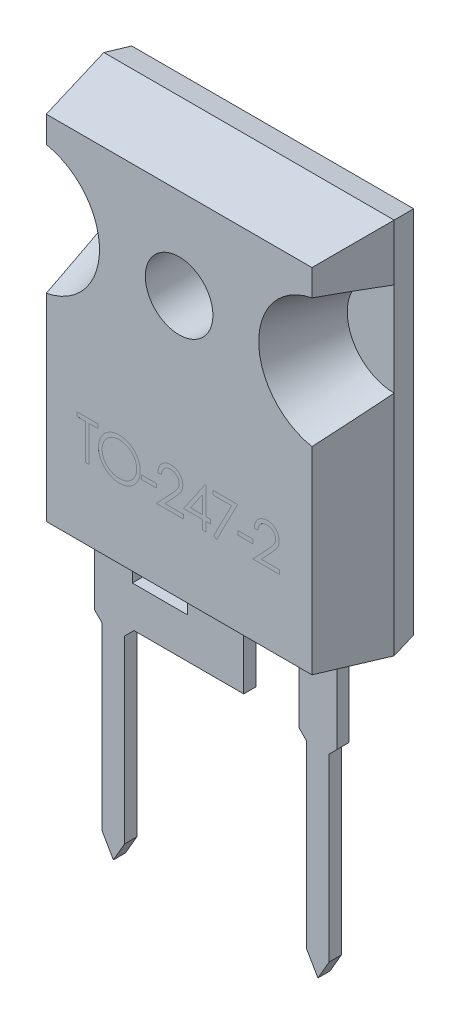
SolidWorks part; units mm, degrees
ref_plane "Front Plane" through (0, 0, 0) normal (0, 0, 1) x (1, 0, 0)
ref_plane "Top Plane" through (0, 0, 0) normal (0, 1, 0) x (1, 0, 0)
ref_plane "Right Plane" through (0, 0, 0) normal (1, 0, 0) x (0, 0, -1)
sketch "Sketch1" plane through (0, 0, 0) normal (0, 0, 1) x (1, 0, 0)
  line L1 (-7.75, 10.075) -> (7.75, 10.075)
  line L2 (-7.75, 10.075) -> (-7.75, -10.075)
  line L3 (-7.75, -10.075) -> (7.75, -10.075)
  line L4 (7.75, 10.075) -> (7.75, -10.075)
  line L5 (-7.75, 10.075) -> (7.75, -10.075) construction
  line L6 (-7.75, -10.075) -> (7.75, 10.075) construction
  point P0 (0, 0)
  dimension "D1" = 15.5
  dimension "D2" = 20.15
extrude "Boss-Extrude1" add sketch "Sketch1" against normal blind 1.27 draft 10 and the other way blind 3.73 draft 10
sketch "Sketch2" plane through (0, 0, 0) normal (0, 0, 1) x (1, 0, 0)
  line L0 (7.75, 10.075) -> (-7.75, 10.075) construction
  line L1 (-5.25, 7.4139) -> (-5.25, 0.8413) construction
  line L2 (-7.75, 10.075) -> (-7.75, -10.075) construction
  line L3 (0, 14.1994) -> (0, -3.2617) construction
  line L4 (7.75, -10.075) -> (7.75, 10.075) construction
  circle A0 centre (0, 4.565) radius 1.805 construction
  circle A1 centre (-7.75, 4.575) radius 2.5
  circle A2 centre (7.75, 4.575) radius 2.5
  dimension "D1" = 5.51
  dimension "D2" = 3.61
  dimension "D3" = 5.5
  dimension "D4" = 5
  dimension "D5" = 2.5
  dimension "D6" = 7.75
extrude "Cut-Extrude1" cut sketch "Sketch2" along normal up to surface (3.73 mm away) draft 15
sketch "Sketch4" plane through (0, 0, 0) normal (0, 0, 1) x (1, 0, 0)
  line L0 (7.75, 10.075) -> (-7.75, 10.075) construction
  circle A0 centre (0, 4.565) radius 1.805
  dimension "D1" = 3.61
  dimension "D2" = 5.51
extrude "Cut-Extrude2" cut sketch "Sketch4" along normal through all both and the other way through all
sketch "Sketch5" plane through (0, 0, 0) normal (0, 1, 0) x (1, 0, 0)
  line L0 (-9.5483, -1.13) -> (8.845, -1.13) construction
  line L1 (7.5261, 1.27) -> (-7.5261, 1.27) construction
  line L2 (0, 2.9425) -> (0, -4.6836) construction
  line L3 (-6.47, -1.13) -> (-4.45, -1.13)
  line L4 (-6.47, -1.13) -> (-6.47, -1.78)
  line L5 (-6.47, -1.78) -> (-4.45, -1.78)
  line L6 (-4.45, -1.13) -> (-4.45, -1.78)
  line L7 (-5.46, -1.13) -> (-5.46, -1.78) construction
  line L8 (6.47, -1.13) -> (6.47, -1.78)
  line L9 (6.47, -1.13) -> (4.45, -1.13)
  line L10 (4.45, -1.13) -> (4.45, -1.78)
  line L11 (6.47, -1.78) -> (4.45, -1.78)
  line L13 (-1.5, -1.13) -> (1.5, -1.13)
  line L14 (-1.5, -1.13) -> (-1.5, -1.78)
  line L15 (-1.5, -1.78) -> (1.5, -1.78)
  line L16 (1.5, -1.13) -> (1.5, -1.78)
  point P21 (0, -1.13)
  dimension "D1" = 2.4
  dimension "D2" = 2.02
  dimension "D3" = 0.65
  dimension "D4" = 5.46
  dimension "D5" = 3
extrude "Boss-Extrude2" add sketch "Sketch5" against normal blind 14.07
sketch "Sketch6" plane through (0, 0, 1.78) normal (0, 0, 1) x (1, 0, 0)
  line L0 (1.5, -14.07) -> (-6.47, -14.07)
  line L1 (-6.47, -14.07) -> (-6.47, -11.9156)
  line L2 (-6.47, -14.07) -> (-6.47, -9.7611) construction
  line L3 (-6.47, -11.9156) -> (1.5, -11.9156)
  line L4 (1.5, -14.07) -> (1.5, -9.7611) construction
  line L5 (1.5, -11.9156) -> (1.5, -14.07)
extrude "Boss-Extrude3" add sketch "Sketch6" against normal up to surface (0.65 mm away) up to face at (-5.46, -11.9729, 1.13)
sketch "Sketch7" plane through (0, 0, -1.27) normal (0, 0, -1) x (-1, 0, 0)
  line L0 (-7.75, 10.075) -> (7.75, 10.075) construction
  line L1 (-5.9, 9.225) -> (5.9, 9.225)
  line L2 (-6.9, 8.225) -> (-6.9, -3.855)
  line L3 (-6.9, -3.855) -> (6.9, -3.855)
  line L4 (6.9, 8.225) -> (6.9, -3.855)
  line L5 (-6.9, 9.225) -> (6.9, -3.855) construction
  line L6 (-6.9, -3.855) -> (6.9, 9.225) construction
  line L7 (7.75, 7.075) -> (7.75, 2.075) construction
  circle A0 centre (0, 4.565) radius 1.805 construction
  circle A1 centre (0, 4.565) radius 1.805
  arc A2 (-6.9, 8.225) -> (-5.9, 9.225) centre (-5.9, 8.225) cw
  arc A3 (6.9, 8.225) -> (5.9, 9.225) centre (5.9, 8.225) ccw
  point P0 (0, 2.685)
  dimension "D4" = 1
  dimension "D1" = 13.08
  dimension "D2" = 0.85
  dimension "D3" = 0.85
extrude "Boss-Extrude4" add sketch "Sketch7" along normal blind 0.0001
sketch "Sketch8" plane through (0, 0, 1.78) normal (0, 0, 1) x (1, 0, 0)
  line L0 (-6.06, -14.07) -> (-6.06, -24.1858)
  line L1 (-6.47, -14.07) -> (1.5, -14.07) construction
  line L2 (-6.06, -24.1858) -> (-5.46, -25.225)
  line L3 (-5.46, -25.225) -> (-4.86, -24.1858)
  line L4 (-4.86, -24.1858) -> (-4.86, -14.07)
  line L5 (-7.75, -10.075) -> (7.75, -10.075) construction
  line L6 (-5.46, -9.7611) -> (-5.46, -27.3304) construction
  line L7 (-6.47, -9.7611) -> (-4.45, -9.7611) construction
  line L8 (0, -9.7611) -> (0, -26.1766) construction
  line L9 (-1.5, -9.7611) -> (1.5, -9.7611) construction
  line L10 (-6.06, -14.07) -> (-4.86, -14.07)
  line L11 (6.06, -14.07) -> (6.06, -24.1858)
  line L12 (6.06, -24.1858) -> (5.46, -25.225)
  line L13 (5.46, -25.225) -> (4.86, -24.1858)
  line L14 (4.86, -24.1858) -> (4.86, -14.07)
  line L15 (6.06, -14.07) -> (4.86, -14.07)
  dimension "D1" = 15.15
  dimension "D2" = 1.2
  dimension "D3" = 60
extrude "Boss-Extrude5" add sketch "Sketch8" against normal up to surface (0.65 mm away) up to face at (5.46, -11.9729, 1.13)
chamfer "Chamfer1" distance 0.5 angle 45 4 edges at (4.86, -14.07, 1.455) (6.06, -14.07, 1.455) (-4.86, -14.07, 1.455) (-6.06, -14.07, 1.455)
sketch "Sketch9" plane through (0, 0, 3.73) normal (0, 0, 1) x (1, 0, 0)
  line L0 (-7.0923, -5.6406) -> (7.0923, -5.6406) construction
  line L1 (-7.0923, 1.1379) -> (-7.0923, -9.4173) construction
  line L2 (7.0923, -9.4173) -> (7.0923, 1.1379) construction
  text T0 "TO-247-2" font "Century Gothic" height in points 8
extrude "Cut-Extrude3" cut sketch "Sketch9" against normal blind 0.0001
